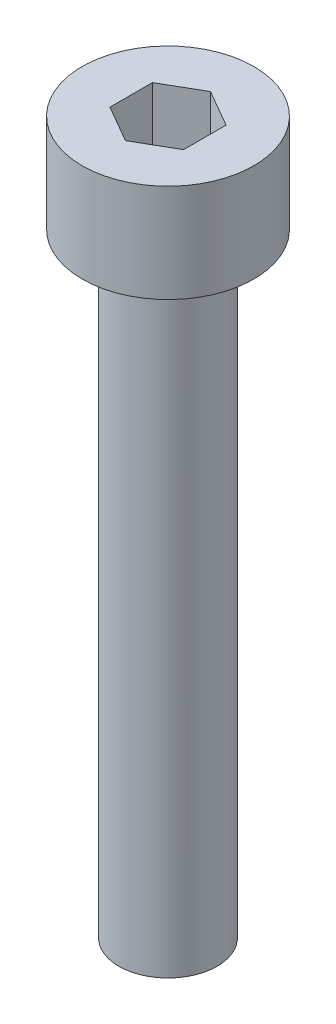
SolidWorks part; units mm, degrees
ref_plane "Front Plane" through (0, 0, 0) normal (0, 0, 1) x (1, 0, 0)
ref_plane "Top Plane" through (0, 0, 0) normal (0, 1, 0) x (1, 0, 0)
ref_plane "Right Plane" through (0, 0, 0) normal (1, 0, 0) x (0, 0, -1)
sketch "Sketch2" plane through (0, 0, 0) normal (0, 1, 0) x (1, 0, 0)
  line L1 (0, 1.7321) -> (-1.5, 0.866)
  line L2 (-1.5, 0.866) -> (-1.5, -0.866)
  line L3 (-1.5, -0.866) -> (0, -1.7321)
  line L4 (0, -1.7321) -> (1.5, -0.866)
  line L5 (1.5, -0.866) -> (1.5, 0.866)
  line L6 (1.5, 0.866) -> (0, 1.7321)
  circle A0 centre (0, 0) radius 3.5
  circle A1 centre (0, 0) radius 1.5 construction
  dimension "D1" = 7
  dimension "D2" = 3
extrude "Boss-Extrude1" add sketch "Sketch2" along normal blind 4
sketch "Sketch3" plane through (0, 0, 0) normal (0, -1, 0) x (1, 0, 0)
  circle A0 centre (0, 0) radius 2
  dimension "D1" = 4
extrude "Boss-Extrude2" add sketch "Sketch3" along normal blind 25
